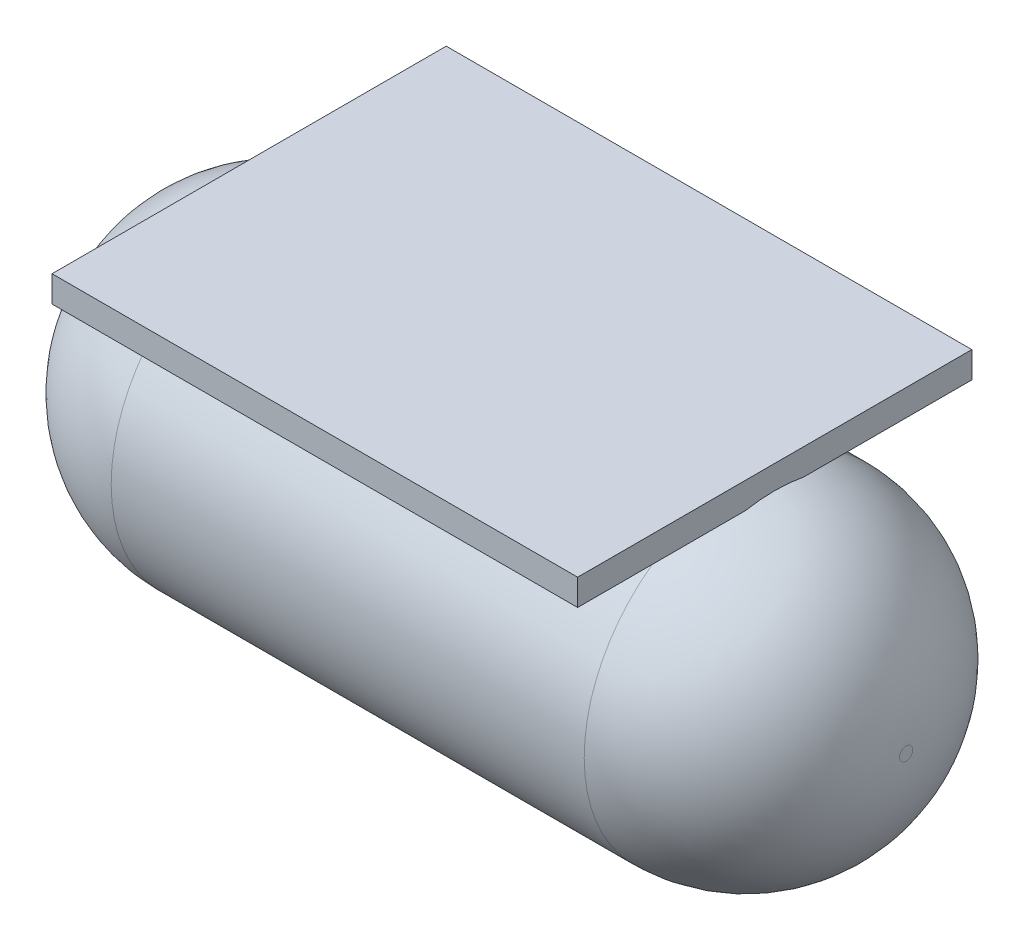
SolidWorks part; units mm, degrees
material "Plain Carbon Steel"
ref_plane "Front Plane" through (0, 0, 0) normal (0, 0, 1) x (1, 0, 0)
ref_plane "Top Plane" through (0, 0, 0) normal (0, 1, 0) x (1, 0, 0)
ref_plane "Right Plane" through (0, 0, 0) normal (1, 0, 0) x (0, 0, -1)
sketch "Sketch1" plane through (0, 0, 0) normal (0, 1, 0) x (1, 0, 0)
  line L1 (0, 0) -> (10.16, 0)
  line L2 (0, 0) -> (0, 7.62)
  line L3 (0, 7.62) -> (10.16, 7.62)
  line L4 (10.16, 0) -> (10.16, 7.62)
  dimension "D1" = 10.16
  dimension "D2" = 7.62
extrude "Boss-Extrude1" add sketch "Sketch1" along normal blind 0.508
ref_plane "Plane1" through (12.7, 0, 0) normal (1, 0, 0) x (0, 0, -1)
sketch "Sketch2" plane through (12.7, 0, 0) normal (1, 0, 0) x (0, 0, -1)
  line L0 (3.81, -3.0806) -> (3.81, 0) construction
  line L1 (0, 0) -> (7.62, 0) construction
  circle A0 centre (3.81, -3.0806) radius 3.175
  dimension "D1" = 6.35
extrude "Boss-Extrude2" add sketch "Sketch2" against normal blind 15.24
fillet "Fillet1" radius 3.048 1 edges at (-2.54, -3.0806, -6.985)
fillet "Fillet2" radius 3.048 1 edges at (12.7, -3.0806, -6.985)
